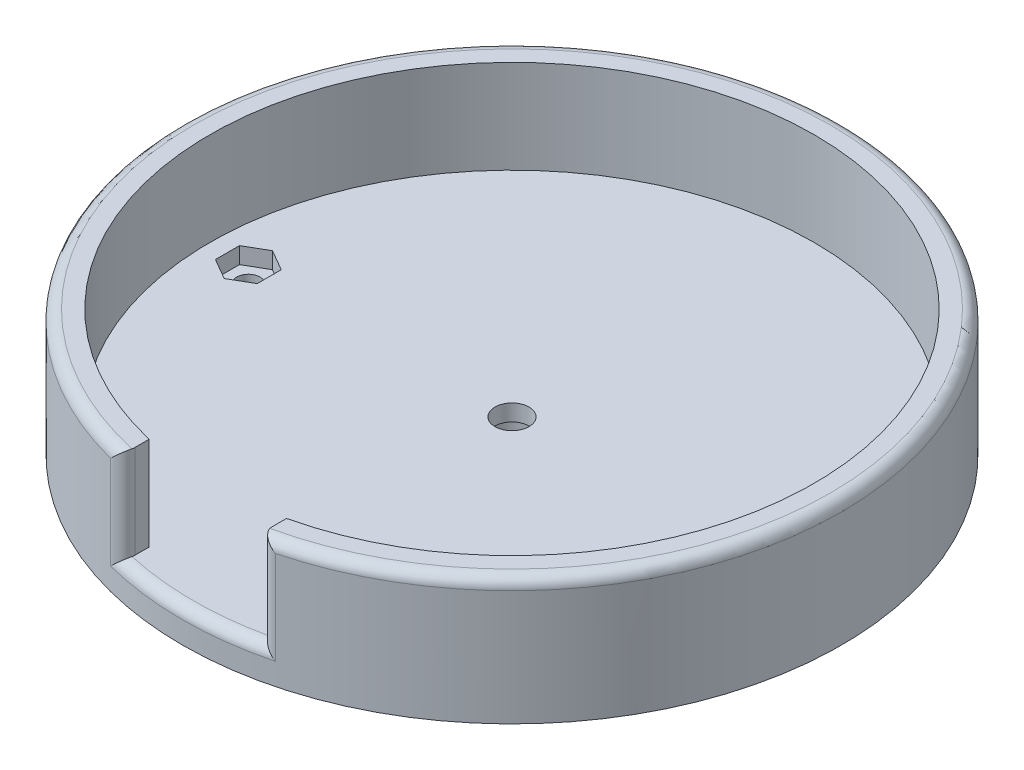
SolidWorks part; units mm, degrees
material "PEI"
ref_plane "Front Plane" through (0, 0, 0) normal (0, 0, 1) x (1, 0, 0)
ref_plane "Top Plane" through (0, 0, 0) normal (0, 1, 0) x (1, 0, 0)
ref_plane "Right Plane" through (0, 0, 0) normal (1, 0, 0) x (0, 0, -1)
sketch "Sketch1" plane through (0, 0, 0) normal (0, 1, 0) x (1, 0, 0)
  line L0 (0, 0) -> (0, -31618.1629) construction
  circle A0 centre (0, 0) radius 60
  circle A1 centre (-48, 0) radius 2.1
  circle A2 centre (0, 0) radius 3.1
  circle A3 centre (48, 0) radius 2.1
  dimension "D1" = 6.2
  dimension "D2" = 4.2
  dimension "D4" = 120
  dimension "D3" = 48
extrude "Boss-Extrude1" add sketch "Sketch1" along normal blind 6
sketch "Sketch2" plane through (0, 6, 0) normal (0, 1, 0) x (1, 0, 0)
  line L0 (0, 0) -> (0, 50000) construction
  line L1 (-51.8, 2.1939) -> (-51.8, -2.1939)
  line L2 (-51.8, -2.1939) -> (-48, -4.3879)
  line L3 (-48, -4.3879) -> (-44.2, -2.1939)
  line L4 (-44.2, -2.1939) -> (-44.2, 2.1939)
  line L5 (-44.2, 2.1939) -> (-48, 4.3879)
  line L6 (-48, 4.3879) -> (-51.8, 2.1939)
  line L7 (48, 4.3879) -> (51.8, 2.1939)
  line L8 (44.2, 2.1939) -> (48, 4.3879)
  line L9 (44.2, -2.1939) -> (44.2, 2.1939)
  line L10 (48, -4.3879) -> (44.2, -2.1939)
  line L11 (51.8, -2.1939) -> (48, -4.3879)
  line L12 (51.8, 2.1939) -> (51.8, -2.1939)
  circle A0 centre (-48, 0) radius 3.8 construction
  circle A1 centre (48, 0) radius 3.8 construction
  point P1 (-51.8, 0)
  dimension "D1" = 7.6
extrude "Cut-Extrude1" cut sketch "Sketch2" against normal blind 3
sketch "Sketch3" plane through (0, 0, 0) normal (0, -1, 0) x (1, 0, 0)
  circle A0 centre (0, 0) radius 4.8
  dimension "D1" = 9.6
extrude "Cut-Extrude2" cut sketch "Sketch3" against normal blind 3
sketch "Sketch4" plane through (0, 6, 0) normal (0, 1, 0) x (1, 0, 0)
  circle A0 centre (0, 0) radius 60
  circle A1 centre (0, 0) radius 55
  dimension "D1" = 120
  dimension "D2" = 5
extrude "Boss-Extrude2" add sketch "Sketch4" along normal blind 17
sketch "Sketch5" plane through (0, 6, 0) normal (0, 1, 0) x (1, 0, 0)
  line L1 (12.5, -67.5) -> (-12.5, -67.5)
  line L2 (12.5, -67.5) -> (12.5, -32.5)
  line L3 (12.5, -32.5) -> (-12.5, -32.5)
  line L4 (-12.5, -67.5) -> (-12.5, -32.5)
  line L5 (12.5, -67.5) -> (-12.5, -32.5) construction
  line L6 (12.5, -32.5) -> (-12.5, -67.5) construction
  point P0 (0, -50)
  dimension "D1" = 50
  dimension "D2" = 25
  dimension "D3" = 35
extrude "Cut-Extrude3" cut sketch "Sketch5" along normal through all
fillet "Fillet1" radius 2 4 edges at (0, 23, -60) (12.5, 14.5, 58.6835) (-12.5, 14.5, 58.6835) (0, 6, 60)
